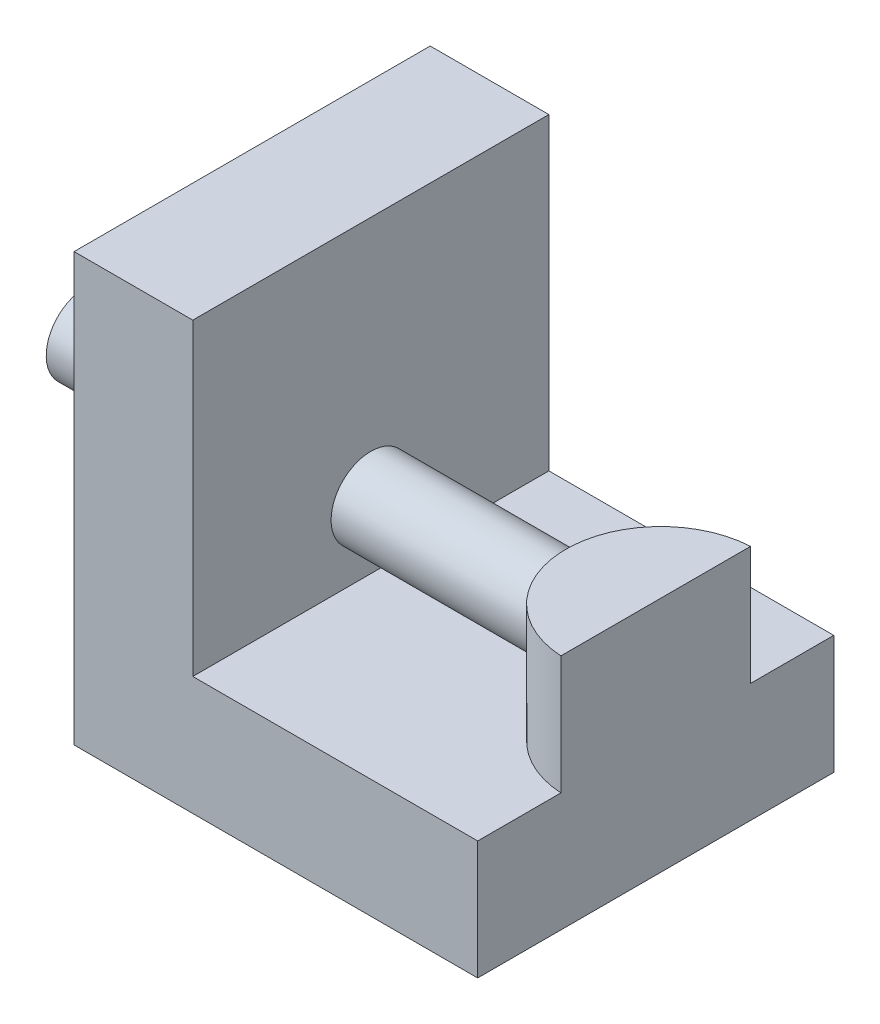
SolidWorks part; units mm, degrees
ref_plane "前视基准面" through (0, 0, 0) normal (0, 0, 1) x (1, 0, 0)
ref_plane "上视基准面" through (0, 0, 0) normal (0, 1, 0) x (1, 0, 0)
ref_plane "右视基准面" through (0, 0, 0) normal (1, 0, 0) x (0, 0, -1)
other "Configuration Table"
sketch "草图2" plane through (0, 0, 0) normal (0, 0, 1) x (1, 0, 0)
  line L0 (0, 0) -> (0, -36)
  line L1 (0, -36) -> (60, -36)
  line L2 (60, -36) -> (60, -26)
  line L3 (60, -26) -> (10, -26)
  line L4 (10, -26) -> (10, 0)
  line L5 (10, 0) -> (0, 0)
  dimension "D1" = 36
  dimension "D2" = 60
  dimension "D3" = 10
  dimension "D4" = 10
extrude "凸台-拉伸1" add sketch "草图2" along normal mid plane 30
sketch "草图3" plane through (0, -26, 0) normal (0, 1, 0) x (1, 0, 0)
  circle A0 centre (34.4318, 0) radius 8
  dimension "D1" = 16
extrude "凸台-拉伸2" add sketch "草图3" along normal mid plane 20
sketch "草图4" plane through (0, -26, 0) normal (0, 1, 0) x (1, 0, 0)
  line L0 (60, 15) -> (10, 15) construction
  line L1 (34.0029, 15) -> (60, 15)
  line L2 (34.0029, 15) -> (34.0029, -15)
  line L3 (34.0029, -15) -> (60, -15)
  line L4 (60, 15) -> (60, -15)
extrude "切除-拉伸3" cut sketch "草图4" against normal through all both and the other way through all
sketch "草图5" plane through (10, 0, 0) normal (1, 0, 0) x (0, 0, -1)
  circle A0 centre (0, -20.4236) radius 3.3494
extrude "凸台-拉伸13" add sketch "草图5" along normal up to surface (24.0029 mm away) and the other way blind 24 from offset 0 contours A0 up to face at (34.0029, -26, 0)
